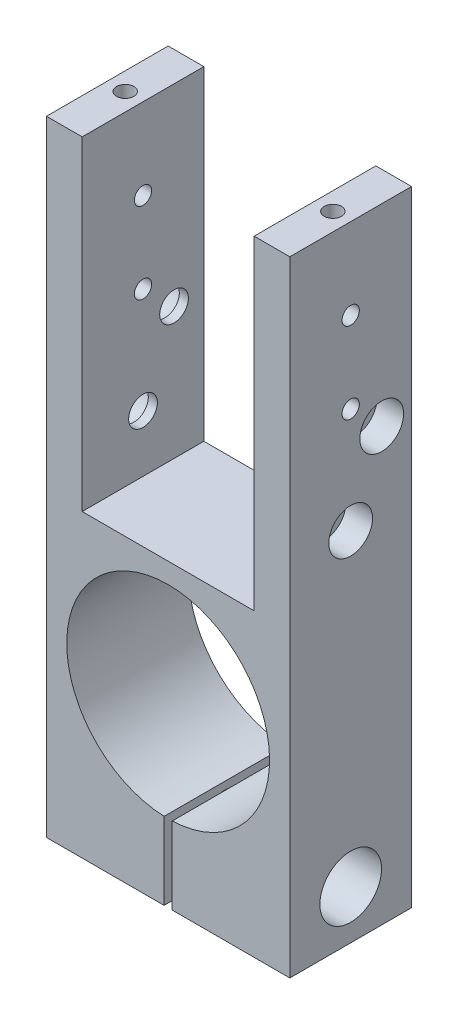
SolidWorks part; units mm, degrees
material "6061 Alloy"
ref_plane "Front Plane" through (0, 0, 0) normal (0, 0, 1) x (1, 0, 0)
ref_plane "Top Plane" through (0, 0, 0) normal (0, 1, 0) x (1, 0, 0)
ref_plane "Right Plane" through (0, 0, 0) normal (1, 0, 0) x (0, 0, -1)
sketch "Sketch1" plane through (0, 0, 0) normal (0, 1, 0) x (1, 0, 0)
  line L1 (-19.05, -9.525) -> (19.05, -9.525)
  line L2 (-19.05, -9.525) -> (-19.05, 9.525)
  line L3 (-19.05, 9.525) -> (19.05, 9.525)
  line L4 (19.05, -9.525) -> (19.05, 9.525)
  line L5 (-19.05, -9.525) -> (19.05, 9.525) construction
  line L6 (-19.05, 9.525) -> (19.05, -9.525) construction
  point P0 (0, 0)
  dimension "D1" = 38.1
  dimension "D2" = 19.05
extrude "Boss-Extrude1" add sketch "Sketch1" along normal mid plane 97.79
sketch "Sketch2" plane through (0, 0, 9.525) normal (0, 0, 1) x (1, 0, 0)
  line L0 (-19.05, 48.895) -> (19.05, 48.895) construction
  line L1 (13.462, 48.895) -> (-13.462, 48.895)
  line L2 (13.462, 48.895) -> (13.462, -1.905)
  line L3 (13.462, -1.905) -> (-13.462, -1.905)
  line L4 (-13.462, 48.895) -> (-13.462, -1.905)
  line L5 (-19.05, 48.895) -> (-19.05, -48.895) construction
  line L6 (19.05, 48.895) -> (19.05, -48.895) construction
  line L7 (-19.05, -48.895) -> (19.05, -48.895) construction
  circle A0 centre (0, -20.955) radius 15.875
  dimension "D1" = 5.588
  dimension "D2" = 5.588
  dimension "D3" = 19.05
  dimension "D4" = 27.94
extrude "Cut-Extrude1" cut sketch "Sketch2" against normal through all
hole_wizard "CBORE for #8 Socket Head Cap Screw1" positions "Sketch5" profile "Sketch4" counterbore size "#8" standard "ANSI Inch" end condition up to next
sketch "Sketch5" plane through (19.05, 0, 0) normal (1, 0, 0) x (0, 0, -1)
  line L0 (-9.525, 48.895) -> (9.525, 48.895) construction
  line L1 (4.8601, 18.7183) -> (4.8601, 6.985)
  line L2 (4.8601, 6.985) -> (0, 6.985)
  line L3 (0, 6.985) -> (4.8601, 6.985)
  line L5 (0, 6.985) -> (4.8601, 18.7183)
  point P0 (0, 6.985)
  point P5 (4.8601, 18.7183)
  dimension "D1" = 41.91
  dimension "D2" = 12.7
  dimension "D3" = 67.5
sketch "Sketch4" plane through (19.05, 6.985, 0) normal (0, 1, 0) x (0, 0, -1)
  line L0 (0, 0) -> (0, 38.1)
  line L1 (0, 38.1) -> (2.2479, 38.1)
  line L3 (2.2479, 38.1) -> (2.2479, 4.1656)
  line L4 (2.2479, 4.1656) -> (3.429, 4.1656)
  line L5 (3.429, 4.1656) -> (3.429, 0)
  line L7 (3.429, 0) -> (0, 0)
  line L11 (0, -6.35) -> (0, 107.95) construction
  dimension "Thru Hole Dia." = 4.4958
  dimension "Thru Hole Depth" = 38.1
  dimension "C'Bore Dia." = 6.858
  dimension "C'Bore Depth" = 4.1656
hole_wizard "#6-32 Tapped Hole1" positions "Sketch7" profile "Sketch6" tap size "#6-32" standard "ANSI Inch" end condition up to next
sketch "Sketch7" plane through (19.05, 0, 0) normal (1, 0, 0) x (0, 0, -1)
  line L0 (-9.525, 48.895) -> (9.525, 48.895) construction
  point P0 (0, 23.495)
  point P2 (0, 36.195)
  dimension "D1" = 12.7
  dimension "D2" = 12.7
sketch "Sketch6" plane through (19.05, 23.495, 0) normal (0, 1, 0) x (0, 0, -1)
  line L0 (0, 0) -> (0, 38.1)
  line L1 (0, 38.1) -> (1.3525, 38.1)
  line L2 (1.3525, 38.1) -> (1.3525, 0)
  line L5 (1.3525, 0) -> (0, 0)
  line L11 (0, -6.35) -> (0, 107.95) construction
  dimension "Thru Tap Drill Dia." = 2.7051
  dimension "Thru Tap Drill Depth" = 38.1
cosmetic thread "Hole Thread1" parameters "D2"=3.5052
cosmetic thread "Hole Thread2" parameters "D2"=3.5052
hole_wizard "#6-32 Tapped Hole2" positions "Sketch9" profile "Sketch8" tap size "#6-32" standard "ANSI Inch"
sketch "Sketch9" plane through (0, 48.895, 0) normal (0, 1, 0) x (1, 0, 0)
  line L0 (19.05, -9.525) -> (19.05, 9.525) construction
  point P0 (16.256, 0)
  dimension "D1" = 2.794
sketch "Sketch8" plane through (16.256, 48.895, 0) normal (1, 0, 0) x (0, 0, 1)
  line L0 (0, 0) -> (0, 11.8871)
  line L1 (0, 11.8871) -> (1.3525, 11.0744)
  line L2 (1.3525, 11.0744) -> (1.3525, 0)
  line L5 (1.3525, 0) -> (0, 0)
  line L10 (0, 11.8871) -> (-1.3526, 11.0744) construction
  line L11 (0, -6.35) -> (0, 107.95) construction
  dimension "Tap Drill Dia." = 2.7051
  dimension "Tap Drill Depth" = 11.0744
  dimension "Drill Angle" = 118
cosmetic thread "Hole Thread3" parameters "D1"=11.0744, "D2"=3.5052
hole_wizard "#8-32 Tapped Hole1" positions "Sketch15" profile "Sketch14" tap size "#8-32" standard "ANSI Inch"
sketch "Sketch15" plane through (0, -48.895, 0) normal (0, -1, 0) x (-1, 0, 0)
  line L2 (-19.05, 9.525) -> (19.05, 9.525) construction
  line L4 (19.05, -9.525) -> (-19.05, -9.525) construction
  point P6 (-10.16, 6.985)
  point P17 (-6.35, -6.985)
  dimension "D1" = 6.35
  dimension "D2" = 10.16
  dimension "D3" = 2.54
  dimension "D4" = 2.54
sketch "Sketch14" plane through (10.16, -48.895, -6.985) normal (1, 0, 0) x (0, 0, -1)
  line L0 (0, 0) -> (0, 13.3314)
  line L1 (0, 13.3314) -> (1.7272, 12.2936)
  line L2 (1.7272, 12.2936) -> (1.7272, 0)
  line L5 (1.7272, 0) -> (0, 0)
  line L10 (0, 13.3314) -> (-1.7272, 12.2936) construction
  line L11 (0, -6.35) -> (0, 107.95) construction
  dimension "Tap Drill Dia." = 3.4544
  dimension "Tap Drill Depth" = 12.2936
  dimension "Drill Angle" = 118
cosmetic thread "Hole Thread4" parameters "D1"=8.3312, "D2"=4.1656
cosmetic thread "Hole Thread5" parameters "D1"=8.3312, "D2"=4.1656
mirror "Mirror3" about plane through (0, 0, 0) normal (1, 0, 0) of "#6-32 Tapped Hole2", "CBORE for #8 Socket Head Cap Screw1", "#6-32 Tapped Hole1"
hole_wizard "CBORE for 1/4 Socket Head Cap Screw2" positions "Sketch19" profile "Sketch18" counterbore size "1/4" standard "ANSI Inch" end condition up to next
sketch "Sketch19" plane through (19.05, 0, 0) normal (1, 0, 0) x (0, 0, -1)
  line L0 (-9.525, -48.895) -> (9.525, -48.895) construction
  point P0 (0, -41.275)
  dimension "D1" = 7.62
sketch "Sketch18" plane through (19.05, -41.275, 0) normal (0, 1, 0) x (0, 0, -1)
  line L0 (0, 0) -> (0, 38.1)
  line L1 (0, 38.1) -> (3.2512, 38.1)
  line L3 (3.2512, 38.1) -> (3.2512, 7.112)
  line L4 (3.2512, 7.112) -> (4.826, 7.112)
  line L5 (4.826, 7.112) -> (4.826, 0)
  line L7 (4.826, 0) -> (0, 0)
  line L11 (0, -6.35) -> (0, 107.95) construction
  dimension "Thru Hole Dia." = 6.5024
  dimension "Thru Hole Depth" = 38.1
  dimension "C'Bore Dia." = 9.652
  dimension "C'Bore Depth" = 7.112
sketch "Sketch20" plane through (0, 0, 9.525) normal (0, 0, 1) x (1, 0, 0)
  line L1 (-0.635, -33.6009) -> (0.635, -33.6009)
  line L2 (-0.635, -33.6009) -> (-0.635, -51.3809)
  line L3 (-0.635, -51.3809) -> (0.635, -51.3809)
  line L4 (0.635, -33.6009) -> (0.635, -51.3809)
  line L5 (-0.635, -33.6009) -> (0.635, -51.3809) construction
  line L6 (-0.635, -51.3809) -> (0.635, -33.6009) construction
  point P0 (0, -42.4909)
  dimension "D1" = 1.27
  dimension "D2" = 17.78
extrude "Cut-Extrude4" cut sketch "Sketch20" against normal up to next
sketch "Sketch21" plane through (-19.05, 0, 0) normal (-1, 0, 0) x (0, 0, 1)
  line L1 (-5.588, -48.895) -> (5.588, -48.895)
  line L2 (-5.588, -48.895) -> (-5.588, -33.655)
  line L3 (-5.588, -33.655) -> (5.588, -33.655)
  line L4 (5.588, -48.895) -> (5.588, -33.655)
  line L5 (-5.588, -48.895) -> (5.588, -33.655) construction
  line L6 (-5.588, -33.655) -> (5.588, -48.895) construction
  point P0 (0, -41.275)
  dimension "D1" = 11.176
  dimension "D2" = 15.24
extrude "Cut-Extrude5" cut sketch "Sketch21" against normal blind 6.35
mirror "Mirror4" about plane through (0, 0, 0) normal (1, 0, 0) of "#8-32 Tapped Hole1"
